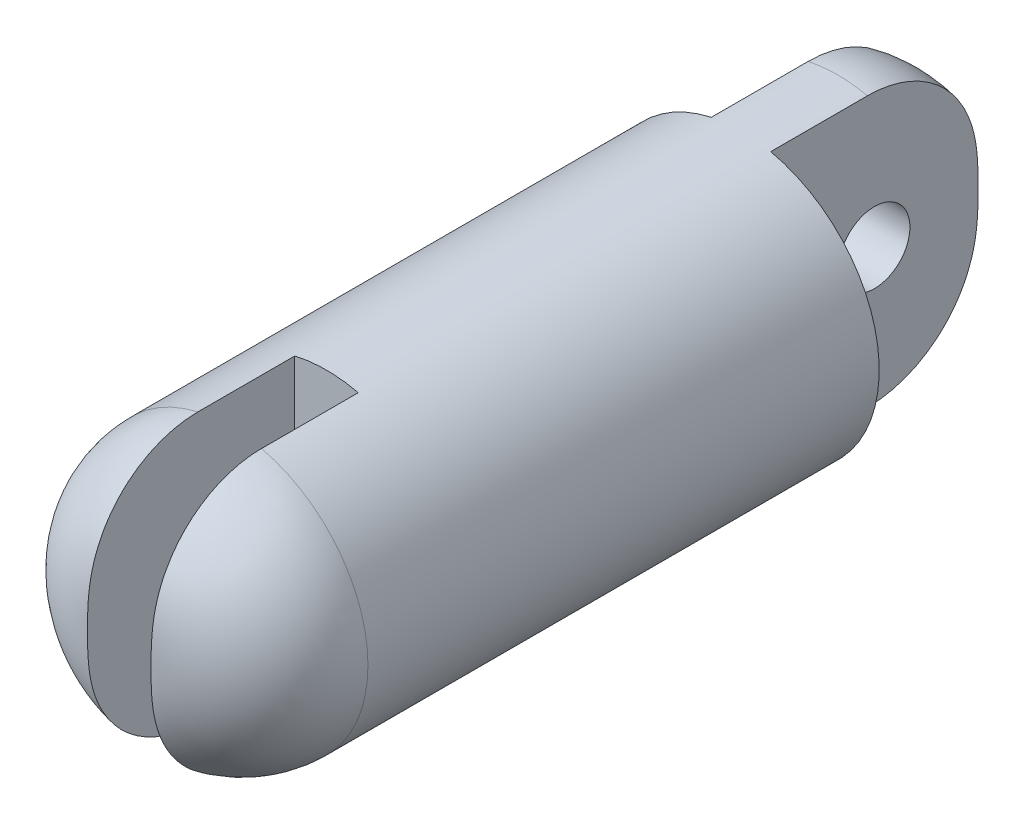
SolidWorks part; units mm, degrees
ref_plane "Front Plane" through (0, 0, 0) normal (0, 0, 1) x (1, 0, 0)
ref_plane "Top Plane" through (0, 0, 0) normal (0, 1, 0) x (1, 0, 0)
ref_plane "Right Plane" through (0, 0, 0) normal (1, 0, 0) x (0, 0, -1)
sketch "Sketch1" plane through (0, 0, 0) normal (0, 0, 1) x (1, 0, 0)
  circle A0 centre (0, 0) radius 100
  point P2 (0, 0)
  dimension "D2" = 200
extrude "Boss-Extrude1" add sketch "Sketch1" along normal blind 600
fillet "Fillet2" radius 80 1 edges at (100, 0, 600)
ref_plane "Plane1" through (0, 0, 600) normal (0, 0, 1) x (1, 0, 0)
sketch "Sketch2" plane through (0, 0, 600) normal (0, 0, 1) x (1, 0, 0)
  line L8 (-23, -115.931) -> (23, -115.931)
  line L9 (-23, -115.931) -> (-23, 115.931)
  line L10 (-23, 115.931) -> (23, 115.931)
  line L11 (23, -115.931) -> (23, 115.931)
  line L12 (-23, -115.931) -> (23, 115.931) construction
  line L13 (-23, 115.931) -> (23, -115.931) construction
  point P9 (0, 0)
  dimension "D2" = 46
extrude "Cut-Extrude1" cut sketch "Sketch2" against normal blind 150
sketch "Sketch3" plane through (0, 0, 0) normal (1, 0, 0) x (0, 0, -1)
  line L0 (-599.9437, 0) -> (-449.9585, 0) construction
  line L1 (-600, 55) -> (-600, -55) construction
  circle A0 centre (-524.9511, 0) radius 20.1551
extrude "Boss-Extrude2" add sketch "Sketch3" along normal mid plane 60
sketch "Sketch4" plane through (0, 0, 0) normal (0, 0, -1) x (-1, 0, 0)
  line L1 (-21.5143, -97.6583) -> (21.5143, -97.6583)
  line L2 (-21.5143, -97.6583) -> (-21.5143, 97.6583)
  line L3 (-21.5143, 97.6583) -> (21.5143, 97.6583)
  line L4 (21.5143, -97.6583) -> (21.5143, 97.6583)
  line L5 (-21.5143, -97.6583) -> (21.5143, 97.6583) construction
  line L6 (-21.5143, 97.6583) -> (21.5143, -97.6583) construction
  circle A0 centre (0, 0) radius 100 construction
  circle A2 centre (0, 0) radius 100
  point P0 (0, 0)
extrude "Cut-Extrude2" cut sketch "Sketch4" against normal blind 150
fillet "Fillet3" radius 80 2 edges at (0, -100, 0) (0, 100, 0)
sketch "Sketch5" plane through (21.5143, 0, 0) normal (1, 0, 0) x (0, 0, -1)
  line L0 (0, 0) -> (-150, 0) construction
  line L1 (-150, -97.6583) -> (-150, 97.6583) construction
  circle A0 centre (-75, 0) radius 25.7363
extrude "Cut-Extrude3" cut sketch "Sketch5" against normal blind 520
